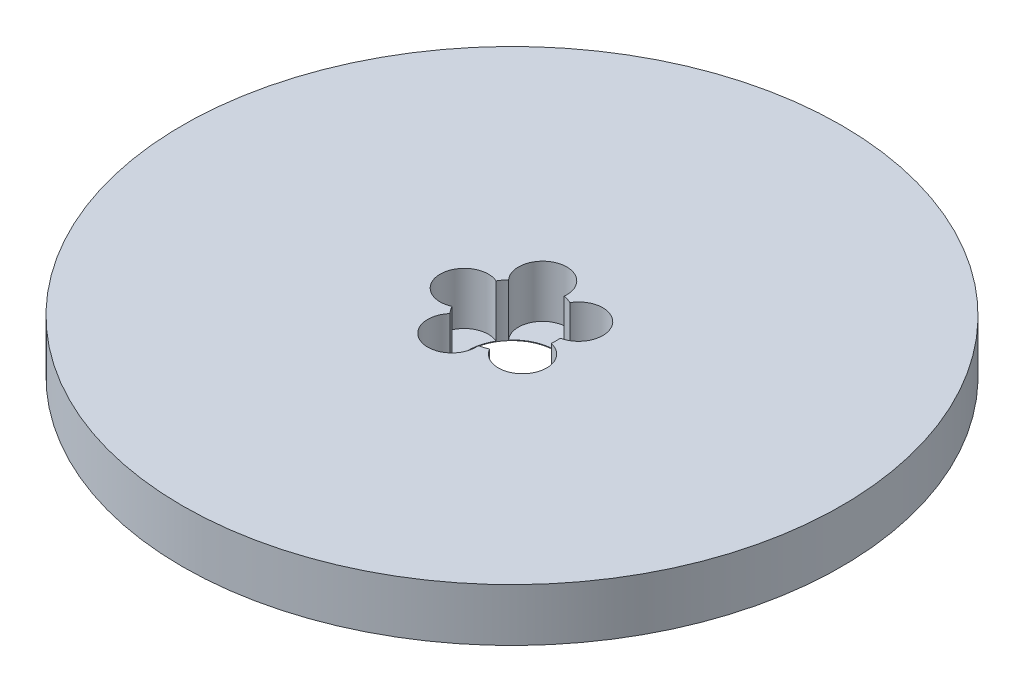
SolidWorks part; units mm, degrees
ref_plane "Front Plane" through (0, 0, 0) normal (0, 0, 1) x (1, 0, 0)
ref_plane "Top Plane" through (0, 0, 0) normal (0, 1, 0) x (1, 0, 0)
ref_plane "Right Plane" through (0, 0, 0) normal (1, 0, 0) x (0, 0, -1)
sketch "Sketch1" plane through (0, 0, 0) normal (0, 1, 0) x (1, 0, 0)
  circle A0 centre (0, 0) radius 37.5
  dimension "FLANGE_OD" = 75
extrude "Boss-Extrude1" add sketch "Sketch1" along normal blind 6
sketch "Sketch2" plane through (0, 0, 0) normal (0, 1, 0) x (1, 0, 0)
  circle A0 centre (0, 0) radius 5
  dimension "BORE_D" = 10
extrude "Cut-Extrude1" cut sketch "Sketch2" along normal through all
sketch "Sketch3" plane through (0, 6, 0) normal (0, 1, 0) x (1, 0, 0)
  circle A0 centre (0, 0) radius 5.4288 construction
  circle A1 centre (-5.4288, 0) radius 2.7468
  dimension "BOLT_D" = 5.4935
  dimension "BOLT_PCD" = 10.8575
extrude "Cut-Extrude2" cut sketch "Sketch3" against normal blind 5.9322
pattern_circular "CirPattern1" count 5 over 360 about axis through (0, 0, 0) along (0, 1, 0) of "Cut-Extrude2"
